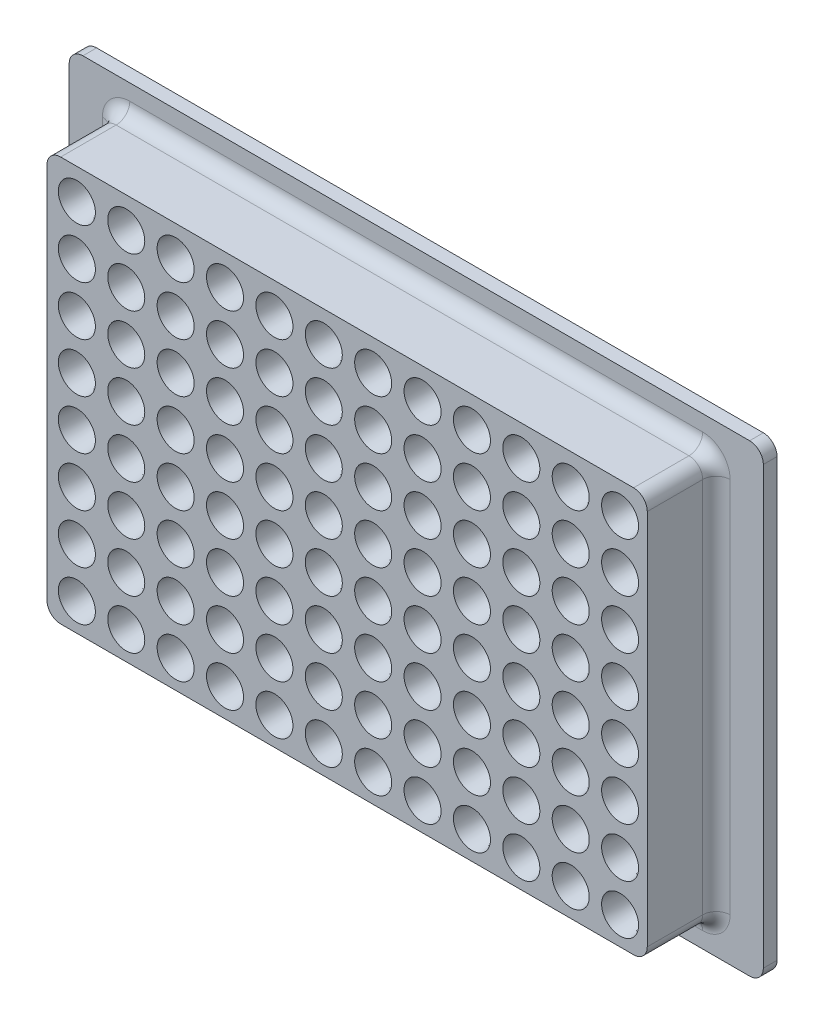
SolidWorks part; units mm, degrees
ref_plane "Front Plane" through (0, 0, 0) normal (0, 0, 1) x (1, 0, 0)
ref_plane "Top Plane" through (0, 0, 0) normal (0, 1, 0) x (1, 0, 0)
ref_plane "Right Plane" through (0, 0, 0) normal (1, 0, 0) x (0, 0, -1)
sketch "Sketch1" plane through (0, 0, 0) normal (0, 0, 1) x (1, 0, 0)
  line L1 (0, 0) -> (126.5, 0)
  line L2 (0, 0) -> (0, 84.5)
  line L3 (0, 84.5) -> (126.5, 84.5)
  line L4 (126.5, 0) -> (126.5, 84.5)
  dimension "D1" = 84.5
  dimension "D2" = 126.5
extrude "Boss-Extrude1" add sketch "Sketch1" along normal blind 2.5
sketch "Sketch3" plane through (0, 0, 2.5) normal (0, 0, 1) x (1, 0, 0)
  line L0 (0, 0) -> (126.5, 0) construction
  line L1 (8.55, 79.1) -> (117.95, 79.1)
  line L2 (8.55, 79.1) -> (8.55, 5.4)
  line L3 (8.55, 5.4) -> (117.95, 5.4)
  line L4 (117.95, 79.1) -> (117.95, 5.4)
  line L5 (0, 84.5) -> (0, 0) construction
  point P4 (63.25, 5.4)
  point P7 (63.25, 0)
  point P8 (8.55, 42.25)
  point P11 (0, 42.25)
  dimension "D1" = 73.7
  dimension "D2" = 109.4
extrude "Boss-Extrude2" add sketch "Sketch3" along normal blind 12.6
fillet "Fillet1" radius 2.5 12 edges at (126.5, 0, 1.25) (0, 0, 1.25) (126.5, 84.5, 1.25) (0, 84.5, 1.25) (63.25, 5.4, 2.5) (117.95, 42.25, 2.5) (8.55, 5.4, 8.8) (117.95, 5.4, 8.8) (117.95, 79.1, 8.8) (8.55, 79.1, 8.8) (63.25, 79.1, 2.5) (8.55, 42.25, 2.5)
sketch "Sketch2" plane through (0, 0, 15.1) normal (0, 0, 1) x (1, 0, 0)
  line L0 (0, 82) -> (0, 2.5) construction
  line L1 (124, 84.5) -> (2.5, 84.5) construction
  circle A0 centre (14, 73.5) radius 3.375
  dimension "D1" = 6.75
  dimension "D2" = 14
  dimension "D3" = 11
extrude "Cut-Extrude1" cut sketch "Sketch2" against normal blind 13 draft 7.5
pattern_linear "LPattern1" count 12 spacing 9 along (1, 0, 0) count 8 spacing 9 along (0, -1, 0) of "Cut-Extrude1"
